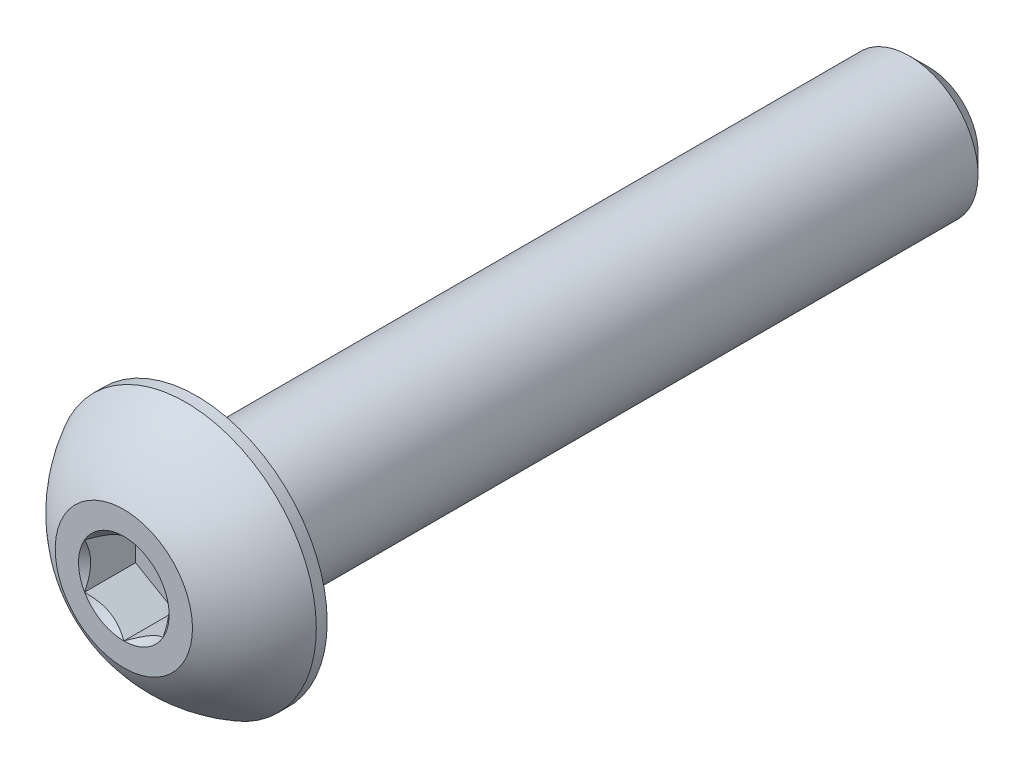
SolidWorks part; units mm, degrees
material "Alloy Steel"
ref_plane "Front" through (0, 0, 0) normal (0, 0, 1) x (1, 0, 0)
ref_plane "Top" through (0, 0, 0) normal (0, 1, 0) x (1, 0, 0)
ref_plane "Right" through (0, 0, 0) normal (1, 0, 0) x (0, 0, -1)
sketch "Sketch1" plane through (0, 0, 0) normal (1, 0, 0) x (0, 0, -1)
  line L2 (2.2098, 2.0828) -> (24.4348, 2.0828)
  line L3 (24.4348, 2.0828) -> (24.4348, 0)
  line L4 (24.4348, 0) -> (2.2098, 0)
  line L6 (1.8783, 3.9624) -> (2.2098, 3.9624) construction
  line L7 (24.4348, 2.0828) -> (24.4348, -2.0828) construction
  line L8 (0, 0) -> (2.2098, 0) construction
  line L9 (2.2098, 3.9624) -> (2.2098, -3.9624) construction
  line L11 (2.2098, 2.0828) -> (2.2098, 0)
  line L13 (0, 1.1906) -> (0, -1.1906) construction
  line L14 (0, 1.1906) -> (0, 2.0828) construction
  arc A3 (0, 2.0828) -> (1.8783, 3.9624) centre (3.9638, 0) cw construction
revolve "Revolve1" add sketch "Sketch1" angle 360 mid plane about L4
sketch "Sketch3" plane through (0, 0, -24.4348) normal (0, 0, -1) x (-1, 0, 0)
  circle A0 centre (0, 0) radius 2.0828
curve "Helix/Spiral1" pitch 0.7937 height 23.0188 turns 29
sketch "Sketch2" plane through (0, 0, 0) normal (1, 0, 0) x (0, 0, -1)
  line L0 (24.4348, 2.0828) -> (25.1293, 2.0828)
  line L1 (25.1293, 2.0828) -> (24.8317, 1.5672)
  line L2 (24.8317, 1.5672) -> (24.7325, 1.5672)
  line L3 (24.7325, 1.5672) -> (24.4348, 2.0828)
  line L4 (24.5836, 1.825) -> (24.9805, 1.825) construction
  dimension "D1" = 60
  dimension "D2" = 0.0992
  dimension "D3" = 0.3969
chamfer "Chamfer1" distance 0.5953 angle 45 1 edges at (0, 2.0828, -24.4348)
sweep "Cut-Sweep1" [suppressed] cut profiles "Sketch2" path "Helix/Spiral1"
sketch "Sketch7" plane through (0, 0, 0) normal (1, 0, 0) x (0, 0, -1)
  line L6 (1.8783, 3.9624) -> (2.2098, 3.9624) construction
  line L8 (0, 0) -> (2.2098, 0) construction
  line L11 (2.2098, 3.9624) -> (2.2098, -3.9624) construction
  line L12 (1.8783, 3.9624) -> (2.2098, 3.9624)
  line L13 (0, 0) -> (2.2098, 0)
  line L14 (0, 1.1906) -> (0, -1.1906) construction
  line L15 (2.2098, 3.9624) -> (2.2098, 0)
  line L16 (0, 2.0828) -> (0, 0)
  arc A2 (1.8783, 3.9624) -> (0, 2.0828) centre (3.9638, 0) ccw construction
  arc A3 (1.8783, 3.9624) -> (0, 2.0828) centre (3.9638, 0) ccw
revolve "Revolve2" add sketch "Sketch7" angle 360 mid plane about L13
sketch "Sketch5" plane through (0, 0, 0) normal (0, 0, 1) x (1, 0, 0)
  line L1 (1.1906, -0.6874) -> (1.1906, 0.6874)
  line L2 (1.1906, 0.6874) -> (0, 1.3748)
  line L3 (0, 1.3748) -> (-1.1906, 0.6874)
  line L4 (-1.1906, 0.6874) -> (-1.1906, -0.6874)
  line L5 (-1.1906, -0.6874) -> (0, -1.3748)
  line L6 (0, -1.3748) -> (1.1906, -0.6874)
  circle A0 centre (0, 0) radius 1.1906 construction
extrude "Cut-Extrude2" cut sketch "Sketch5" against normal blind 1.5469
sketch "Sketch6" plane through (0, 0, 0) normal (0, 0, 1) x (1, 0, 0)
  circle A0 centre (0, 0) radius 1.3748
extrude "Cut-Extrude3" cut sketch "Sketch6" against normal blind 1.5469 draft 45
sketch "Sketch9" [suppressed] plane through (0, 0, -2.2098) normal (0, 0, 1) x (1, 0, 0)
  circle A2 centre (0, 0) radius 2.0828
extrude "Boss-Extrude2" [suppressed] add sketch "Sketch9" against normal offset from surface (3.175 mm away) 22.225
sketch "Sketch10" plane through (0, 0, 0) normal (1, 0, 0) x (0, 0, -1)
  line L0 (24.4348, 2.0828) -> (24.4348, -2.0828) construction
  point P0 (23.2442, -2.0828)
  dimension "D1" = 1.1906
equation "\"D3@Helix/Spiral1\" = \"Lg@Sketch1\" + \"D4@Helix/Spiral1\""
equation "\"D2@Sketch2\" = \"D4@Helix/Spiral1\" * .125"
equation "\"D3@Sketch2\" = \"D4@Helix/Spiral1\" * .5"
equation "\"D1@Chamfer1\" = \"D4@Helix/Spiral1\" * .75"
equation "\"D1@Cut-Extrude2\" = \"Head Ht@Sketch1\" * .7"
equation "\"D1@Sketch1\" = \"Head Ht@Sketch1\" * .15"
equation "\"D1@Sketch10\" = \"D4@Helix/Spiral1\" * 1.5"
equation "\"D1@Cut-Extrude3\" = \"D1@Cut-Extrude2\""
